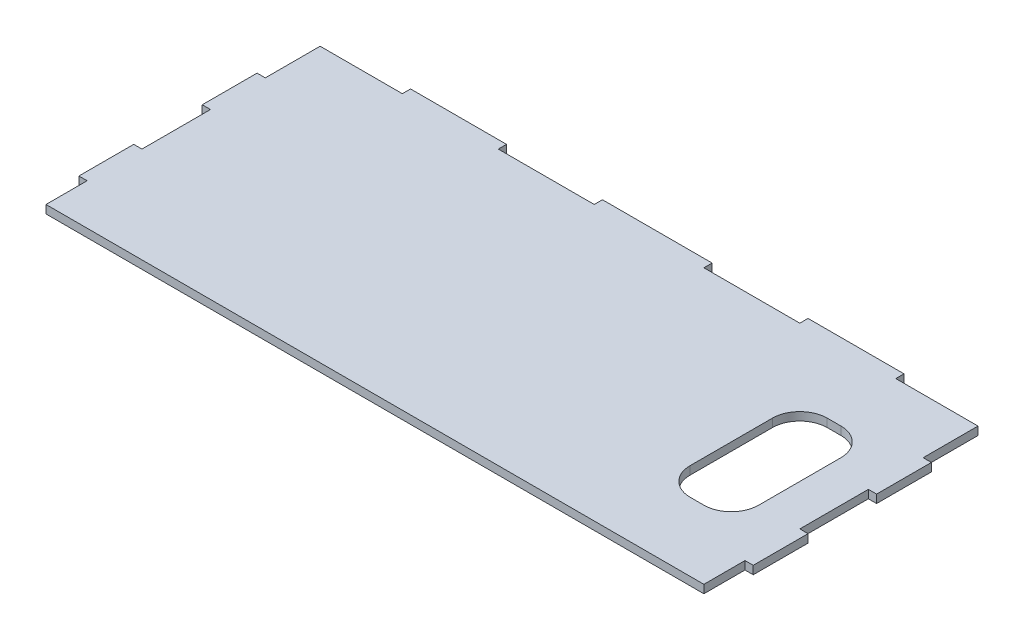
SolidWorks part; units mm, degrees
ref_plane "Front Plane" through (0, 0, 0) normal (0, 0, 1) x (1, 0, 0)
ref_plane "Top Plane" through (0, 0, 0) normal (0, 1, 0) x (1, 0, 0)
ref_plane "Right Plane" through (0, 0, 0) normal (1, 0, 0) x (0, 0, -1)
sketch "Sketch2" plane through (0, 0, 0) normal (0, 0, 1) x (1, 0, 0)
  line L1 (-120, 1.5) -> (120, 1.5)
  line L2 (-120, 1.5) -> (-120, -1.5)
  line L3 (-120, -1.5) -> (120, -1.5)
  line L4 (120, 1.5) -> (120, -1.5)
  dimension "D1" = 3
  dimension "D2" = 240
  dimension "D3" = 120
  dimension "D4" = 1.5
extrude "Boss-Extrude1" add sketch "Sketch2" along normal blind 100 contours L1 L4 L3 L2
sketch "Sketch3" plane through (-120, 0, 0) normal (-1, 0, 0) x (0, 0, 1)
  line L0 (100, 1.5) -> (0, 1.5) construction
  line L1 (20, 1.5) -> (40, 1.5)
  line L2 (20, 1.5) -> (20, -1.5)
  line L3 (20, -1.5) -> (40, -1.5)
  line L4 (40, 1.5) -> (40, -1.5)
  line L5 (100, -1.5) -> (0, -1.5) construction
  line L6 (100, 1.5) -> (100, -1.5) construction
  line L7 (65, 1.5) -> (85, 1.5)
  line L8 (65, 1.5) -> (65, -1.5)
  line L9 (65, -1.5) -> (85, -1.5)
  line L10 (85, 1.5) -> (85, -1.5)
  line L11 (0, 1.5) -> (0, -1.5) construction
  dimension "D1" = 20
  dimension "D2" = 20
  dimension "D3" = 15
  dimension "D4" = 20
extrude "Boss-Extrude2" add sketch "Sketch3" along normal blind 3
extrude "Boss-Extrude3" add sketch "Sketch3<2>" against normal blind 3 from surface starting at face at (120, 0, 50)
sketch "Sketch3<2>" plane through (-120, 0, 0) normal (-1, 0, 0) x (0, 0, 1) same geometry as "Sketch3"
sketch "Sketch4" plane through (0, 0, 0) normal (0, 0, -1) x (-1, 0, 0)
  line L0 (120, 1.5) -> (-120, 1.5) construction
  line L1 (-90, 1.5) -> (-55, 1.5)
  line L2 (-90, 1.5) -> (-90, -1.5)
  line L3 (-90, -1.5) -> (-55, -1.5)
  line L4 (-55, 1.5) -> (-55, -1.5)
  line L5 (120, -1.5) -> (-120, -1.5) construction
  line L6 (-120, 1.5) -> (-120, -1.5) construction
  line L8 (-20, 1.5) -> (20, 1.5)
  line L9 (-20, 1.5) -> (-20, -1.5)
  line L10 (-20, -1.5) -> (20, -1.5)
  line L11 (20, 1.5) -> (20, -1.5)
  line L12 (55, 1.5) -> (90, 1.5)
  line L13 (55, 1.5) -> (55, -1.5)
  line L14 (55, -1.5) -> (90, -1.5)
  line L15 (90, 1.5) -> (90, -1.5)
  dimension "D1" = 30
  dimension "D2" = 35
  dimension "D3" = 40
  dimension "D4" = 35
  dimension "D5" = 35
  dimension "D6" = 35
extrude "Boss-Extrude4" add sketch "Sketch4" along normal blind 3
sketch "Sketch5" plane through (0, 1.5, 0) normal (0, 1, 0) x (1, 0, 0)
  line L0 (90, 0) -> (120, 0) construction
  line L1 (90, -25) -> (95, -25)
  line L2 (80, -35) -> (80, -65)
  line L3 (90, -75) -> (95, -75)
  line L4 (105, -35) -> (105, -65)
  line L5 (-120, -100) -> (120, -100) construction
  line L6 (120, -65) -> (120, -40) construction
  arc A0 (80, -65) -> (90, -75) centre (90, -65) ccw
  arc A1 (95, -75) -> (105, -65) centre (95, -65) ccw
  arc A2 (95, -25) -> (105, -35) centre (95, -35) cw
  arc A3 (90, -25) -> (80, -35) centre (90, -35) ccw
  point P12 (80, -75)
  point P15 (105, -75)
  dimension "D5" = 10
  dimension "D1" = 25
  dimension "D2" = 25
  dimension "D3" = 25
  dimension "D4" = 15
extrude "Cut-Extrude1" cut sketch "Sketch5" against normal blind 3
